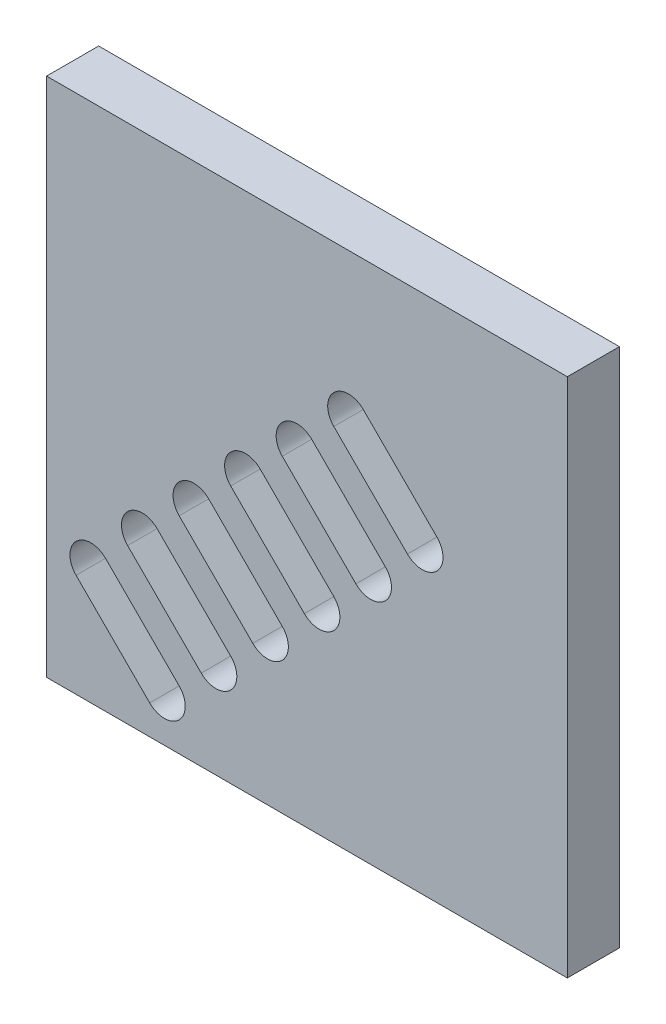
SolidWorks part; units mm, degrees
ref_plane "Front Plane" through (0, 0, 0) normal (0, 0, 1) x (1, 0, 0)
ref_plane "Top Plane" through (0, 0, 0) normal (0, 1, 0) x (1, 0, 0)
ref_plane "Right Plane" through (0, 0, 0) normal (1, 0, 0) x (0, 0, -1)
sketch "Sketch1" plane through (0, 0, 0) normal (0, 0, 1) x (1, 0, 0)
  line L0 (-41.5147, -27.3726) -> (-27.3726, -41.5147) construction
  line L1 (-50, -50) -> (50, -50)
  line L2 (-50, -50) -> (-50, 50)
  line L3 (-50, 50) -> (50, 50)
  line L4 (50, -50) -> (50, 50)
  line L5 (-50, -50) -> (50, 50) construction
  line L6 (-50, 50) -> (50, -50) construction
  line L7 (-38.6863, -24.5442) -> (-24.5442, -38.6863)
  line L8 (-44.3431, -30.201) -> (-30.201, -44.3431)
  arc A0 (-38.6863, -24.5442) -> (-44.3431, -30.201) centre (-41.5147, -27.3726) ccw
  arc A1 (-30.201, -44.3431) -> (-24.5442, -38.6863) centre (-27.3726, -41.5147) ccw
  point P0 (0, 0)
  point P8 (-34.4437, -34.4437)
  dimension "D4" = 4
  dimension "D1" = 100
  dimension "D2" = 100
  dimension "D3" = 20
  dimension "D5" = 22
  dimension "D6" = 45
  dimension "D7" = 0
extrude "Boss-Extrude1" add sketch "Sketch1" along normal mid plane 10
pattern_linear "LPattern2" count 6 spacing 14 along (0.7071, 0.7071, 0) of face at (-25.9584, -42.9289, 0) of face at (-42.9289, -25.9584, 0) of face at (-37.2721, -37.2721, 0) of face at (-31.6152, -31.6152, 0)
